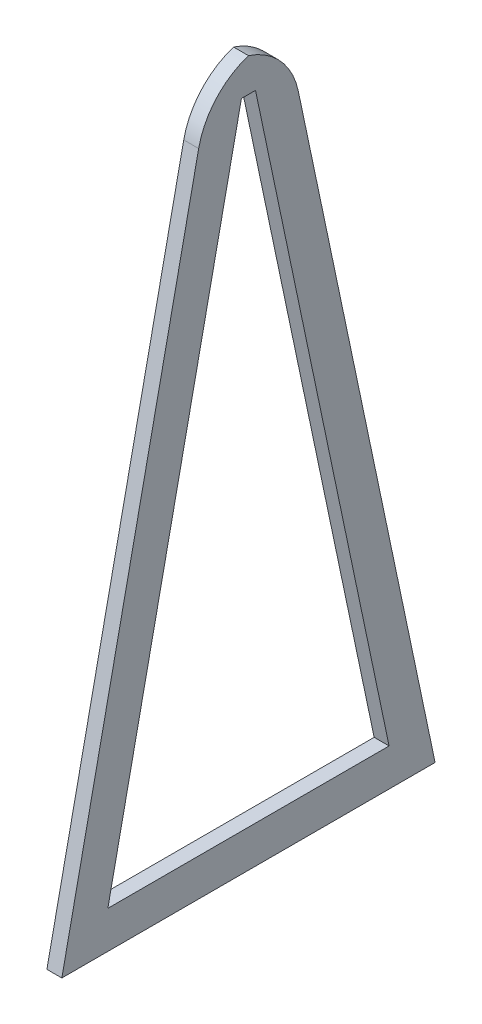
SolidWorks part; units mm, degrees
ref_plane "Front Plane" through (0, 0, 0) normal (0, 0, 1) x (1, 0, 0)
ref_plane "Top Plane" through (0, 0, 0) normal (0, 1, 0) x (1, 0, 0)
ref_plane "Right Plane" through (0, 0, 0) normal (1, 0, 0) x (0, 0, -1)
sketch "Sketch2" plane through (0, 0, 0) normal (0, 1, 0) x (1, 0, 0)
  line L1 (-0.05, 1.25) -> (0.05, 1.25)
  line L2 (-0.05, 1.25) -> (-0.05, -1.25)
  line L3 (-0.05, -1.25) -> (0.05, -1.25)
  line L4 (0.05, 1.25) -> (0.05, -1.25)
  line L5 (-0.05, 1.25) -> (0.05, -1.25) construction
  line L6 (-0.05, -1.25) -> (0.05, 1.25) construction
  point P0 (0, 0)
  point P6 (0, 0)
  dimension "D1" = 0.1
  dimension "D2" = 2.5
extrude "Boss-Extrude1" add sketch "Sketch2" along normal blind 4.75 contours L2 L1 L4 L3
sketch "Sketch3" plane through (0.05, 0, 0) normal (-1, 0, 0) x (0, 0, 1)
  line L0 (-1.25, 0) -> (-0.25, 4.75)
  line L3 (1.25, 0) -> (-1.25, 0)
  line L4 (-0.25, 4.75) -> (0.25, 4.75)
  line L5 (0.25, 4.75) -> (1.25, 0)
  line L7 (-1.25, 4.75) -> (1.25, 4.75) construction
  line L8 (0.0472, 4.5) -> (0.9419, 0.25)
  line L9 (0.9419, 0.25) -> (-0.9419, 0.25)
  line L10 (-0.9419, 0.25) -> (-0.0472, 4.5)
  line L11 (-0.0472, 4.5) -> (0.0472, 4.5)
  point P8 (-2.9753, 2.2642)
  point P10 (0, 0)
  point P12 (4.1074, 0)
  point P13 (0, 0)
  point P16 (0, 0)
  dimension "D1" = 0.5
  dimension "D2" = 0.25
extrude "Cut-Extrude1" cut sketch "Sketch3" along normal up to surface (0.1 mm away) flip side to cut up to face at (-0.05, 2.375, 0)
fillet "Fillet1" radius 0.5 2 edges at (0, 4.75, 0.25) (0, 4.75, -0.25)
ref_axis "Axis1" through (0, 4.7251, 0) along (0, 1, 0)
